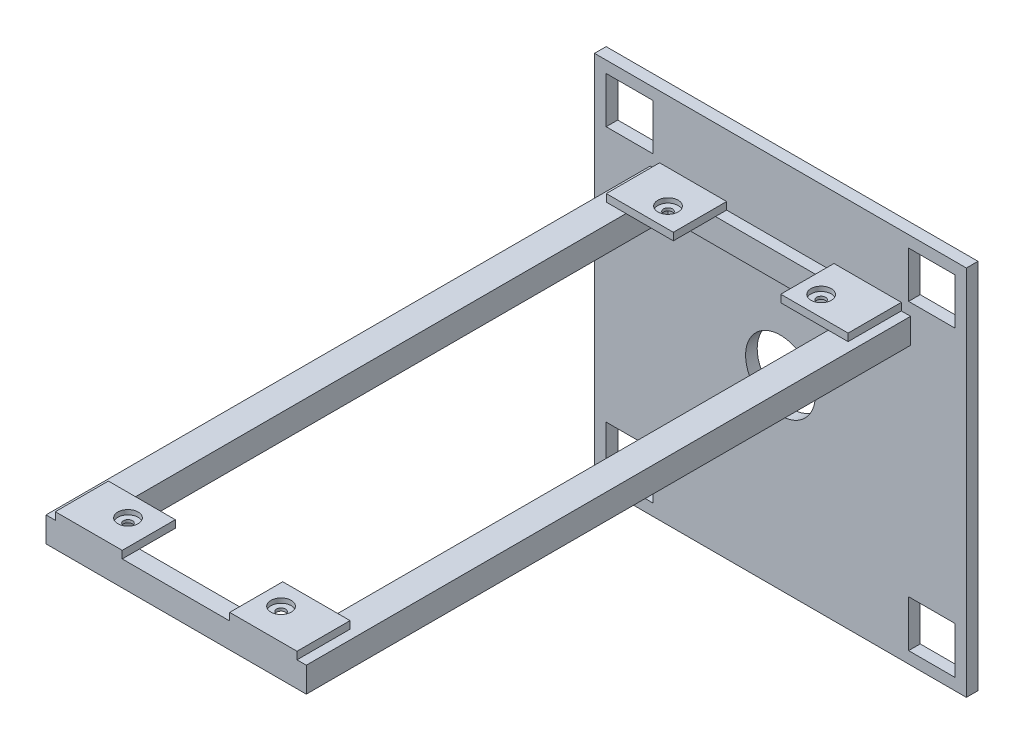
SolidWorks part; units mm, degrees
ref_plane "Front Plane" through (0, 0, 0) normal (0, 0, 1) x (1, 0, 0)
ref_plane "Top Plane" through (0, 0, 0) normal (0, 1, 0) x (1, 0, 0)
ref_plane "Right Plane" through (0, 0, 0) normal (1, 0, 0) x (0, 0, -1)
sketch "Sketch1" plane through (0, 0, 0) normal (0, 0, 1) x (1, 0, 0)
  line L1 (103.2829, -37.7023) -> (1.6829, -37.7023)
  line L2 (103.2829, -37.7023) -> (103.2829, 63.8977)
  line L3 (103.2829, 63.8977) -> (1.6829, 63.8977)
  line L4 (1.6829, -37.7023) -> (1.6829, 63.8977)
  dimension "D1" = 101.6
  dimension "D2" = 101.6
extrude "Boss-Extrude1" add sketch "Sketch1" along normal blind 3.175
sketch "Sketch19" plane through (0, 0, 3.175) normal (0, 0, 1) x (1, 0, 0)
  line L0 (103.2829, 63.8977) -> (1.6829, 63.8977) construction
  line L1 (4.8579, 60.7227) -> (17.6171, 60.7227)
  line L2 (4.8579, 60.7227) -> (4.8579, 48.1127)
  line L3 (4.8579, 48.1127) -> (17.6171, 48.1127)
  line L4 (17.6171, 60.7227) -> (17.6171, 48.1127)
  line L5 (1.6829, 63.8977) -> (1.6829, -37.7023) construction
  line L6 (103.2829, -37.7023) -> (103.2829, 63.8977) construction
  line L7 (100.1079, -34.5273) -> (87.4979, -34.5273)
  line L8 (100.1079, -34.5273) -> (100.1079, -21.7681)
  line L9 (100.1079, -21.7681) -> (87.4979, -21.7681)
  line L10 (87.4979, -34.5273) -> (87.4979, -21.7681)
  line L11 (1.6829, -37.7023) -> (103.2829, -37.7023) construction
  line L13 (100.1079, 60.7227) -> (87.4979, 60.7227)
  line L14 (100.1079, 60.7227) -> (100.1079, 48.1127)
  line L15 (100.1079, 48.1127) -> (87.4979, 48.1127)
  line L16 (87.4979, 60.7227) -> (87.4979, 48.1127)
  line L17 (4.8579, -34.5273) -> (17.6171, -34.5273)
  line L18 (4.8579, -34.5273) -> (4.8579, -21.7681)
  line L19 (4.8579, -21.7681) -> (17.6171, -21.7681)
  line L20 (17.6171, -34.5273) -> (17.6171, -21.7681)
  dimension "D1" = 3.175
  dimension "D2" = 3.175
  dimension "D3" = 3.175
  dimension "D4" = 3.175
extrude "Cut-Extrude1" cut sketch "Sketch19" against normal blind 3.175
sketch "Sketch20" plane through (0, 0, 0) normal (0, 0, -1) x (-1, 0, 0)
  line L0 (-103.2829, 13.0977) -> (-1.6829, 13.0977) construction
  line L1 (-103.2829, -37.7023) -> (-103.2829, 63.8977) construction
  line L2 (-1.6829, 63.8977) -> (-1.6829, -37.7023) construction
hole_wizard "3/4 (0.75) Diameter Hole1" positions "Sketch26" profile "Sketch27" hole size "3/4" standard "ANSI Inch" end condition through all
sketch "Sketch26" plane through (0, 0, 0) normal (0, 0, -1) x (-1, 0, 0)
  line L0 (-103.2829, 13.0977) -> (-1.6829, 13.0977) construction
  point P0 (-52.4829, 13.0977)
sketch "Sketch27" plane through (52.4829, 13.0977, 0) normal (1, 0, 0) x (0, 1, 0)
  line L0 (0, 0) -> (0, 3.175)
  line L1 (0, 3.175) -> (9.525, 3.175)
  line L2 (9.525, 3.175) -> (9.525, 0)
  line L5 (9.525, 0) -> (0, 0)
  line L11 (0, -6.35) -> (0, 107.95) construction
  dimension "Thru Hole Dia." = 19.05
  dimension "Thru Hole Depth" = 3.175
ref_plane "Plane1" through (0, 0, 3.175) normal (0, 0, 1) x (1, 0, 0)
sketch "Sketch29" plane through (0, 0, 3.175) normal (0, 0, 1) x (1, 0, 0)
  line L5 (88.043, 37.9897) -> (16.923, 37.9897)
  line L6 (88.043, 37.9897) -> (88.043, 44.8477)
  line L7 (88.043, 44.8477) -> (16.923, 44.8477)
  line L8 (16.923, 37.9897) -> (16.923, 44.8477)
  line L9 (103.2829, 63.8977) -> (1.6829, 63.8977) construction
  point P0 (0, 0)
  dimension "D1" = 71.12
  dimension "D2" = 0
  dimension "D3" = 19.05
extrude "Boss-Extrude11" add sketch "Sketch29" along normal blind 3.048
sketch "Sketch30" plane through (0, 0, 6.223) normal (0, 0, 1) x (1, 0, 0)
  line L0 (88.043, 44.8477) -> (16.923, 44.8477) construction
  line L1 (88.043, 37.9897) -> (80.0928, 37.9897)
  line L2 (88.043, 37.9897) -> (88.043, 44.8477)
  line L3 (88.043, 44.8477) -> (80.0928, 44.8477)
  line L4 (80.0928, 37.9897) -> (80.0928, 44.8477)
  line L6 (16.923, 37.9897) -> (24.8544, 37.9897)
  line L7 (16.923, 37.9897) -> (16.923, 44.8477)
  line L8 (16.923, 44.8477) -> (24.8544, 44.8477)
  line L9 (24.8544, 37.9897) -> (24.8544, 44.8477)
extrude "Boss-Extrude12" add sketch "Sketch30" along normal blind 162.052
sketch "Sketch31" plane through (80.0928, 0, 0) normal (-1, 0, 0) x (0, 0, 1)
  line L5 (168.275, 37.9897) -> (6.223, 37.9897) construction
  line L6 (168.275, 44.8477) -> (163.5715, 44.8477)
  line L7 (168.275, 44.8477) -> (168.275, 37.9897)
  line L8 (168.275, 37.9897) -> (163.5715, 37.9897)
  line L9 (163.5715, 44.8477) -> (163.5715, 37.9897)
extrude "Boss-Extrude13" add sketch "Sketch31" along normal blind 55.88
sketch "Sketch32" plane through (0, 44.8477, 0) normal (0, 1, 0) x (1, 0, 0)
  line L0 (88.043, -168.275) -> (16.923, -168.275) construction
  line L1 (85.503, -168.275) -> (67.1066, -168.275)
  line L2 (85.503, -168.275) -> (85.503, -153.7758)
  line L3 (85.503, -153.7758) -> (67.1066, -153.7758)
  line L4 (67.1066, -168.275) -> (67.1066, -153.7758)
  line L5 (16.923, -168.275) -> (16.923, -3.175) construction
  line L6 (19.463, -168.275) -> (37.751, -168.275)
  line L7 (19.463, -168.275) -> (19.463, -153.7758)
  line L8 (19.463, -153.7758) -> (37.751, -153.7758)
  line L9 (37.751, -168.275) -> (37.751, -153.7758)
  line L10 (88.043, -168.275) -> (88.043, -3.175) construction
  line L11 (88.043, -3.175) -> (16.923, -3.175) construction
  line L12 (85.503, -3.175) -> (67.1066, -3.175)
  line L13 (85.503, -3.175) -> (85.503, -17.7088)
  line L14 (85.503, -17.7088) -> (67.1066, -17.7088)
  line L15 (67.1066, -3.175) -> (67.1066, -17.7088)
  line L17 (19.463, -3.175) -> (37.7801, -3.175)
  line L18 (19.463, -3.175) -> (19.463, -17.734)
  line L19 (19.463, -17.734) -> (37.7801, -17.734)
  line L20 (37.7801, -3.175) -> (37.7801, -17.734)
  dimension "D1" = 2.54
  dimension "D2" = 2.54
  dimension "D3" = 18.288
  dimension "D4" = 2.54
  dimension "D5" = 2.54
extrude "Boss-Extrude14" add sketch "Sketch32" along normal blind 2.032
hole_wizard "CBORE for #2 Binding Head Machine Screw1" positions "Sketch36" profile "Sketch37" counterbore size "#2" standard "ANSI Inch" end condition through all
sketch "Sketch36" plane through (0, 46.8797, 0) normal (0, 1, 0) x (1, 0, 0)
  point P0 (30.8491, -12.2575)
  point P2 (72.6744, -12.2575)
  point P4 (72.6744, -159.8)
  point P6 (30.8491, -159.8)
sketch "Sketch37" plane through (30.8491, 46.8797, 12.2575) normal (1, 0, 0) x (0, 0, 1)
  line L0 (0, 0) -> (0, 84.582)
  line L1 (0, 84.582) -> (1.2192, 84.582)
  line L3 (1.2192, 84.582) -> (1.2192, 1.27)
  line L4 (1.2192, 1.27) -> (2.7788, 1.27)
  line L5 (2.7788, 1.27) -> (2.7788, 0)
  line L7 (2.7788, 0) -> (0, 0)
  line L11 (0, -6.35) -> (0, 107.95) construction
  dimension "Thru Hole Dia." = 2.4384
  dimension "Thru Hole Depth" = 84.582
  dimension "C'Bore Dia." = 5.5575
  dimension "C'Bore Depth" = 1.27
